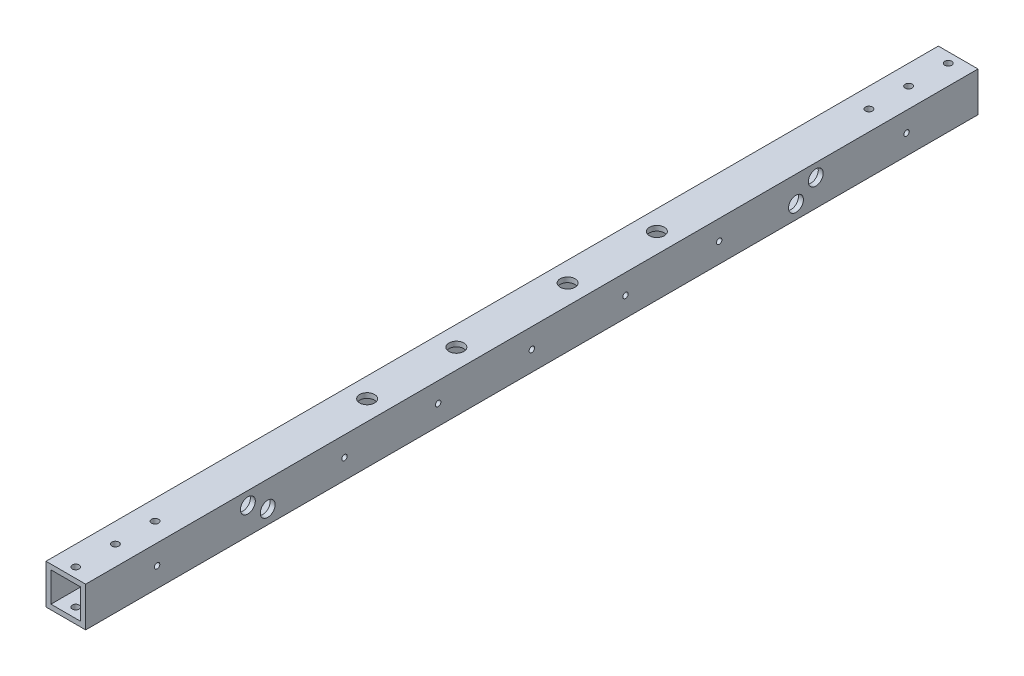
SolidWorks part; units mm, degrees
material "6061-T6 (SS)"
ref_plane "Front Plane" through (0, 0, 0) normal (0, 0, 1) x (1, 0, 0)
ref_plane "Top Plane" through (0, 0, 0) normal (0, 1, 0) x (1, 0, 0)
ref_plane "Right Plane" through (0, 0, 0) normal (1, 0, 0) x (0, 0, -1)
sketch "Sketch1" plane through (0, 0, 0) normal (0, 0, 1) x (1, 0, 0)
  line L1 (-12.7, -12.7) -> (12.7, -12.7)
  line L2 (-12.7, -12.7) -> (-12.7, 12.7)
  line L3 (-12.7, 12.7) -> (12.7, 12.7)
  line L4 (12.7, -12.7) -> (12.7, 12.7)
  line L5 (-12.7, -12.7) -> (12.7, 12.7) construction
  line L6 (-12.7, 12.7) -> (12.7, -12.7) construction
  point P0 (0, 0)
  dimension "D1" = 25.4
  dimension "D2" = 25.4
extrude "Extrude-Thin1" add sketch "Sketch1" along normal blind 571.5 thin thin type one direction reverse wall 3.175
hole_wizard "#8 Clearance Hole1" positions "3DSketch1" profile "Sketch3" hole size "#8" standard "ANSI Inch" end condition through all
sketch3d "3DSketch1"
  line L1 (12.7, 12.7, 0) -> (-12.7, 12.7, 0) construction
  line L6 (0, 12.7, 571.5) -> (0, 12.7, 0) construction
  line L7 (12.7, 12.7, 571.5) -> (-12.7, 12.7, 571.5) construction
  point P57 (0, 12.7, 6.35)
  point P59 (0, 12.7, 31.75)
  point P61 (0, 12.7, 57.15)
  point P63 (0, 12.7, 539.75)
  point P65 (0, 12.7, 514.35)
  point P67 (0, 12.7, 565.15)
  dimension "D1" = 25.4
  dimension "D2" = 25.4
  dimension "D3" = 6.35
  dimension "D4" = 25.4
  dimension "D5" = 25.4
  dimension "D6" = 6.35
sketch "Sketch3" plane through (0, 12.7, 565.15) normal (1, 0, 0) x (0, 0, 1)
  line L0 (0, 0) -> (0, 25.4)
  line L1 (0, 25.4) -> (2.2479, 25.4)
  line L2 (2.2479, 25.4) -> (2.2479, 0)
  line L5 (2.2479, 0) -> (0, 0)
  line L11 (0, -6.35) -> (0, 107.95) construction
  dimension "Thru Hole Dia." = 4.4958
  dimension "Thru Hole Depth" = 25.4
hole_wizard "#8-32 Tapped Hole1" positions "Sketch8" profile "Sketch9" tap size "#8-32" standard "ANSI Inch"
sketch "Sketch8" plane through (12.7, -53.975, 285.75) normal (1, 0, 0) x (0, 0, -1)
  point P0 (-240, 53.975)
  point P6 (-120, 53.975)
  point P9 (-60, 53.975)
  point P12 (0, 53.975)
  point P15 (60, 53.975)
  point P18 (120, 53.975)
  point P24 (240, 53.975)
sketch "Sketch9" plane through (12.7, 0, 525.75) normal (0, 1, 0) x (0, 0, -1)
  line L0 (0, 0) -> (0, 13.3314)
  line L1 (0, 13.3314) -> (1.7272, 12.2936)
  line L2 (1.7272, 12.2936) -> (1.7272, 0)
  line L3 (1.7272, 0) -> (0, 0)
  line L4 (0, 13.3314) -> (-1.7272, 12.2936) construction
  line L5 (0, -6.35) -> (0, 107.95) construction
  dimension "Tap Drill Dia." = 3.4544
  dimension "Tap Drill Depth" = 12.2936
  dimension "Drill Angle" = 118
hole_wizard "3/8 (0.375) Diameter Hole2" positions "Sketch12" profile "Sketch13" hole size "3/8" standard "ANSI Inch" end condition through all
sketch "Sketch12" plane through (-12.7, -82.55, 285.75) normal (1, 0, 0) x (0, 0, -1)
  point P0 (-181.864, 86.995)
  point P3 (-169.164, 78.74)
  point P6 (169.164, 78.74)
  point P9 (181.864, 86.995)
  point P12 (181.864, 57.15)
  point P15 (-181.864, 57.15)
sketch "Sketch13" plane through (-12.7, 4.445, 467.614) normal (0, 1, 0) x (0, 0, 1)
  line L0 (0, 0) -> (0, 25.4)
  line L1 (0, 25.4) -> (4.7625, 25.4)
  line L2 (4.7625, 25.4) -> (4.7625, 0)
  line L3 (4.7625, 0) -> (0, 0)
  line L4 (0, -6.35) -> (0, 107.95) construction
  dimension "Thru Hole Dia." = 9.525
  dimension "Thru Hole Depth" = 25.4
hole_wizard "3/8 (0.375) Diameter Hole3" positions "Sketch14" profile "Sketch15" hole size "3/8" standard "ANSI Inch" end condition through all
sketch "Sketch14" plane through (-346.075, 12.7, 285.75) normal (0, 1, 0) x (0, 0, 1)
  point P9 (-92.7735, 346.075)
  point P12 (-35.6235, 346.075)
  point P18 (35.6235, 346.075)
  point P21 (92.7735, 346.075)
  point P24 (-19.05, -346.775)
  point P27 (53.975, -346.775)
  point P30 (127, -346.775)
  point P42 (-381, -114.3)
  point P45 (-381, -130.175)
  point P48 (-381, -146.05)
  point P55 (-381, 114.3)
  point P58 (-381, 98.425)
  point P61 (-381, 82.55)
sketch "Sketch15" plane through (0, 12.7, 192.9765) normal (1, 0, 0) x (0, 0, 1)
  line L0 (0, 0) -> (0, 25.4)
  line L1 (0, 25.4) -> (4.7625, 25.4)
  line L2 (4.7625, 25.4) -> (4.7625, 0)
  line L3 (4.7625, 0) -> (0, 0)
  line L4 (0, -6.35) -> (0, 107.95) construction
  dimension "Thru Hole Dia." = 9.525
  dimension "Thru Hole Depth" = 25.4
